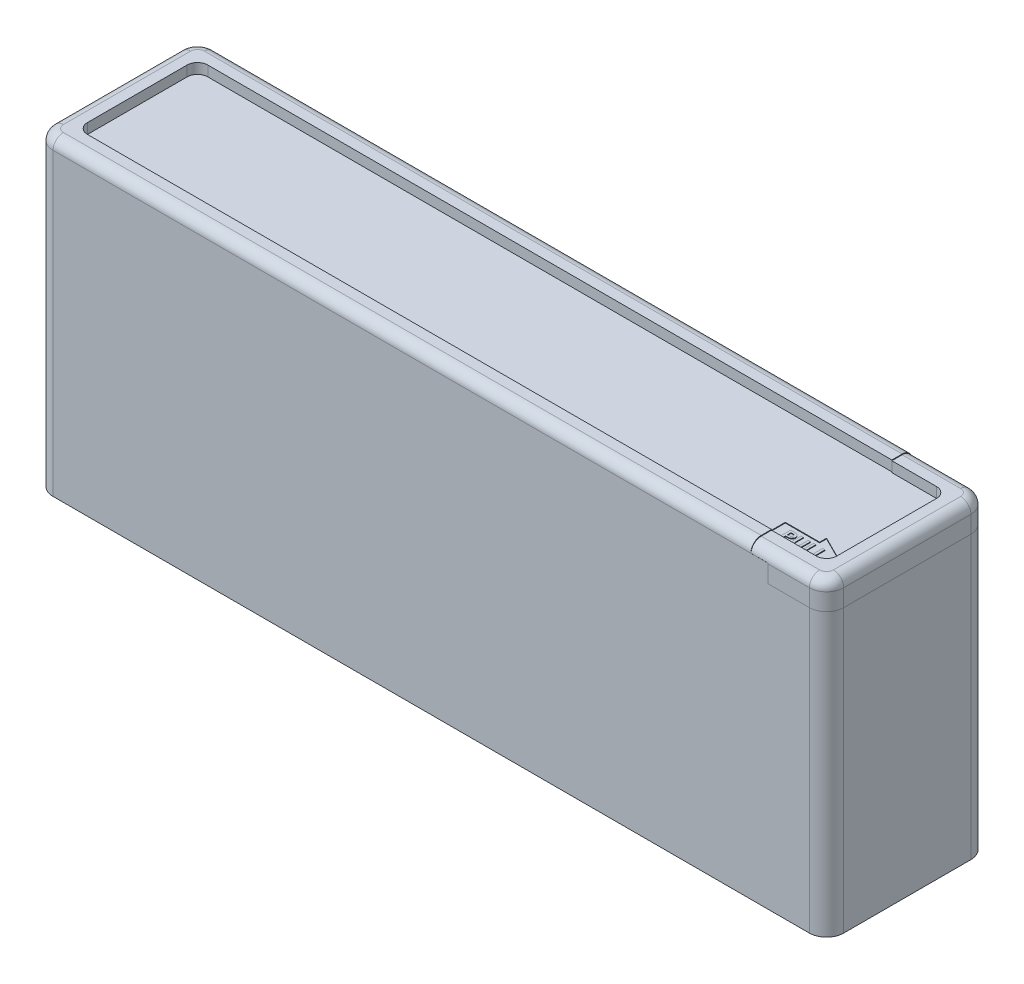
SolidWorks part; units mm, degrees
other "Silica Gel Box"
other "Silica Gel Front"
other "Main Body"
other "Top Slide"
other "Top Trim Add-on"
other "Rectangular Magnet Cover"
other "Circular Magnet Cover 1"
other "Circular Magnet Cover 2"
other "8x1.65 Magnet 2"
other "8x1.65 Magnet 1"
other "20x6x2 Magnet"
other "Drawer"
other "Felt Pad 4"
other "Felt Pad 3"
other "Felt Pad 2"
other "Felt Pad 1"
ref_plane "Front Plane" through (0, 0, 0) normal (0, 0, 1) x (1, 0, 0)
ref_plane "Top Plane" through (0, 0, 0) normal (0, 1, 0) x (1, 0, 0)
ref_plane "Right Plane" through (0, 0, 0) normal (1, 0, 0) x (0, 0, -1)
sketch "Sketch1" plane through (0, 0, 0) normal (0, 1, 0) x (1, 0, 0)
  line L0 (-6, 41) -> (208, 41)
  line L1 (0, 0) -> (202, 0)
  line L2 (0, 0) -> (0, 35)
  line L3 (0, 35) -> (202, 35)
  line L4 (202, 0) -> (202, 35)
  line L5 (0, 0) -> (202, 35) construction
  line L6 (0, 35) -> (202, 0) construction
  line L7 (208, -6) -> (208, 41)
  line L8 (-6, -6) -> (208, -6)
  line L9 (-6, -6) -> (-6, 41)
  point P4 (101, 17.5)
  dimension "D1" = 35
  dimension "D2" = 202
  dimension "D3" = 6
extrude "Boss-Extrude1" add sketch "Sketch1" along normal blind 5
sketch "Sketch2" plane through (0, 0, 0) normal (0, -1, 0) x (1, 0, 0)
  line L4 (-6, 6) -> (-6, -41)
  line L5 (-6, -41) -> (208, -41)
  line L6 (208, -41) -> (208, 6)
  line L7 (208, 6) -> (-6, 6)
  line L8 (-6, 6) -> (-6, -41)
  line L9 (-6, -41) -> (208, -41)
  line L10 (208, -41) -> (208, 6)
  line L11 (208, 6) -> (-6, 6)
  dimension "D1" = 0
extrude "Boss-Extrude2" add sketch "Sketch2" along normal blind 2
sketch "Sketch3" plane through (0, 0, 0) normal (1, 0, 0) x (0, 0, -1)
  line L6 (17.5, 0.5) -> (17.5, 1) construction
  line L8 (0, 0) -> (35, 0) construction
  line L10 (13.5, 0) -> (21.5, 0)
  line L12 (13.5, 1) -> (21.5, 0) construction
  line L13 (13.5, 0) -> (21.5, 1) construction
  arc A1 (21.5, 0) -> (13.5, 0) centre (17.5, -7.5) ccw
  point P4 (17.5, 0.5)
  point P5 (17.5, 0)
  dimension "D1" = 8
  dimension "D2" = 1
extrude "Boss-Extrude3" add sketch "Sketch3" along normal up to surface (202 mm away) up to face at (202, 2.5, -17.5)
sketch "Sketch4" plane through (0, 5, 0) normal (0, 1, 0) x (1, 0, 0)
  line L4 (-6, 41) -> (-6, -6)
  line L5 (-6, -6) -> (208, -6)
  line L6 (208, -6) -> (208, 41)
  line L7 (208, 41) -> (-6, 41)
  line L8 (-6, 41) -> (-6, -6)
  line L9 (-6, -6) -> (208, -6)
  line L10 (208, -6) -> (208, 41)
  line L11 (208, 41) -> (-6, 41)
  line L12 (0, 35) -> (0, 0)
  line L13 (202, 35) -> (0, 35)
  line L14 (202, 0) -> (202, 35)
  line L15 (0, 0) -> (202, 0)
  line L16 (0, 35) -> (0, 0)
  line L17 (202, 35) -> (0, 35)
  line L18 (202, 0) -> (202, 35)
  line L19 (0, 0) -> (202, 0)
  dimension "D1" = 0
  dimension "D2" = 0
extrude "Boss-Extrude4" add sketch "Sketch4" along normal blind 45
sketch "Sketch6" plane through (208, 0, 0) normal (1, 0, 0) x (0, 0, -1)
  line L4 (-6, 50) -> (-6, -2)
  line L5 (-6, -2) -> (41, -2)
  line L6 (41, -2) -> (41, 50)
  line L7 (41, 50) -> (-6, 50)
  line L8 (-6, 50) -> (-6, -2)
  line L9 (-6, -2) -> (41, -2)
  line L10 (41, -2) -> (41, 50)
  line L11 (41, 50) -> (-6, 50)
  dimension "D1" = 0
extrude "Boss-Extrude5" add sketch "Sketch6" along normal blind 16
sketch "Sketch7" plane through (0, 50, 0) normal (0, 1, 0) x (1, 0, 0)
  line L0 (202, 21.5) -> (202, 35) construction
  line L1 (207, 38) -> (202, 38)
  line L2 (207, 38) -> (207, -3)
  line L3 (207, -3) -> (202, -3)
  line L4 (202, 38) -> (202, -3)
  line L5 (207, 38) -> (202, -3) construction
  line L6 (207, -3) -> (202, 38) construction
  line L7 (202, 35) -> (0, 35) construction
  line L8 (0, 0) -> (202, 0) construction
  point P4 (204.5, 17.5)
  dimension "D1" = 3
  dimension "D2" = 3
  dimension "D3" = 5
extrude "Cut-Extrude1" cut sketch "Sketch7" against normal blind 50.1
sketch "Sketch8" plane through (207, 0, 0) normal (-1, 0, 0) x (0, 0, 1)
  line L0 (3, -0.1) -> (3, 50) construction
  line L1 (-38, 50) -> (3, 50)
  line L2 (-38, 50) -> (-38, 0)
  line L3 (-38, 0) -> (3, 0)
  line L4 (3, 50) -> (3, 0)
  line L5 (-38, 50) -> (3, 0) construction
  line L6 (-38, 0) -> (3, 50) construction
  point P4 (-17.5, 25)
  dimension "D1" = 50
extrude "Boss-Extrude6" add sketch "Sketch8" along normal blind 5 separate body
sketch "Sketch9" plane through (207, 0, 0) normal (-1, 0, 0) x (0, 0, 1)
  line L4 (3, 50) -> (-38, 50)
  line L5 (-38, 50) -> (-38, -0.1)
  line L6 (-38, -0.1) -> (3, -0.1)
  line L7 (3, -0.1) -> (3, 50)
  line L8 (3, 50) -> (-38, 50)
  line L9 (-38, 50) -> (-38, -0.1)
  line L10 (-38, -0.1) -> (3, -0.1)
  line L11 (3, -0.1) -> (3, 50)
  dimension "D1" = 0
extrude "Cut-Extrude2" cut sketch "Sketch9" against normal blind 14
sketch "Sketch10" plane through (221, 0, 0) normal (-1, 0, 0) x (0, 0, 1)
  line L0 (3, -0.1) -> (3, 50) construction
  line L1 (-38, 50) -> (3, 50)
  line L2 (-38, 50) -> (-38, 0)
  line L3 (-38, 0) -> (3, 0)
  line L4 (3, 50) -> (3, 0)
  line L5 (-38, 50) -> (3, 0) construction
  line L6 (-38, 0) -> (3, 50) construction
  point P4 (-17.5, 25)
  dimension "D1" = 50
extrude "Boss-Extrude7" add sketch "Sketch10" along normal blind 3 separate body
sketch "Sketch12" plane through (218, 0, 0) normal (-1, 0, 0) x (0, 0, 1)
  line L0 (-35, 47) -> (-35, 3)
  line L1 (-35, 3) -> (0, 3)
  line L2 (0, 3) -> (0, 47)
  line L3 (0, 47) -> (-35, 47)
  line L4 (-38, 50) -> (-38, 0)
  line L5 (-38, 0) -> (3, 0)
  line L6 (3, 0) -> (3, 50)
  line L7 (3, 50) -> (-38, 50)
  line L8 (-38, 50) -> (-38, 0)
  line L9 (-38, 0) -> (3, 0)
  line L10 (3, 0) -> (3, 50)
  line L11 (3, 50) -> (-38, 50)
  dimension "D1" = 0
  dimension "D2" = 3
extrude "Boss-Extrude8" add sketch "Sketch12" along normal blind 11
chamfer "Chamfer1" distance 8 angle 45 4 edges at (212.5, 3, 0) (212.5, 3, -35) (212.5, 47, 0) (212.5, 47, -35)
fillet "Fillet1" radius 3 5 edges at (211.5, -0.1, -38) (221, 24.95, -38) (221, -0.1, -17.5) (221, 24.95, 3) (211.5, -0.1, 3)
fillet "Fillet2" radius 3 5 edges at (221, 25, 3) (214, 0, 3) (221, 0, -17.5) (214, 0, -38) (221, 25, -38)
fillet "Fillet3" radius 3 2 edges at (204.5, 0, -38) (204.5, 0, 3)
sketch "Sketch15" plane through (207, 0, 0) normal (-1, 0, 0) x (0, 0, 1)
  line L0 (-38, 50) -> (-31, 43) construction
  line L1 (-27, 47) -> (-35, 39) construction
  line L2 (-17.5, 50) -> (-17.5, 0) construction
  line L3 (3, 50) -> (-38, 50) construction
  line L4 (-35, 0) -> (0, 0) construction
  line L5 (-17.5, 25) -> (3, 25) construction
  line L8 (3, 3) -> (3, 50) construction
  circle A0 centre (-34.5, 46.5) radius 1.1
  circle A1 centre (-0.5, 46.5) radius 1.1
  circle A4 centre (-0.5, 3.5) radius 1.1
  circle A5 centre (-34.5, 3.5) radius 1.1
  dimension "D1" = 2.2
extrude "Cut-Extrude3" cut sketch "Sketch15" against normal blind 11
sketch "Sketch16" plane through (218, 0, 0) normal (-1, 0, 0) x (0, 0, 1)
  line L0 (-38, 50) -> (-31, 43) construction
  line L1 (-27, 47) -> (-35, 39) construction
  line L2 (-17.5, 25) -> (3, 25) construction
  line L5 (-17.5, 50) -> (-17.5, 0) construction
  line L6 (3, 50) -> (-38, 50) construction
  line L7 (-35, 0) -> (0, 0) construction
  line L8 (-35, 39) -> (-27, 47) construction
  line L9 (-32.8262, 48.1738) -> (-35.1127, 48.7865)
  line L10 (-35.1127, 48.7865) -> (-36.7865, 47.1127)
  line L11 (-36.7865, 47.1127) -> (-36.1738, 44.8262)
  line L12 (-36.1738, 44.8262) -> (-33.8873, 44.2135)
  line L13 (-33.8873, 44.2135) -> (-32.2135, 45.8873)
  line L14 (-32.2135, 45.8873) -> (-32.8262, 48.1738)
  line L15 (-2.1738, 48.1738) -> (0.1127, 48.7865)
  line L16 (-1.1127, 44.2135) -> (-2.7865, 45.8873)
  line L17 (-2.7865, 45.8873) -> (-2.1738, 48.1738)
  line L18 (1.1738, 44.8262) -> (-1.1127, 44.2135)
  line L19 (1.7865, 47.1127) -> (1.1738, 44.8262)
  line L20 (0.1127, 48.7865) -> (1.7865, 47.1127)
  line L33 (3, 3) -> (3, 50) construction
  line L34 (1.7865, 2.8873) -> (1.1738, 5.1738)
  line L35 (1.1738, 5.1738) -> (-1.1127, 5.7865)
  line L36 (-1.1127, 5.7865) -> (-2.7865, 4.1127)
  line L37 (-2.7865, 4.1127) -> (-2.1738, 1.8262)
  line L38 (-2.1738, 1.8262) -> (0.1127, 1.2135)
  line L39 (0.1127, 1.2135) -> (1.7865, 2.8873)
  line L40 (-33.8873, 5.7865) -> (-32.2135, 4.1127)
  line L41 (-32.2135, 4.1127) -> (-32.8262, 1.8262)
  line L42 (-32.8262, 1.8262) -> (-35.1127, 1.2135)
  line L43 (-35.1127, 1.2135) -> (-36.7865, 2.8873)
  line L44 (-36.7865, 2.8873) -> (-36.1738, 5.1738)
  line L45 (-36.1738, 5.1738) -> (-33.8873, 5.7865)
  circle A0 centre (-34.5, 46.5) radius 2.05 construction
  circle A1 centre (-0.5, 46.5) radius 2.05 construction
  circle A4 centre (-0.5, 3.5) radius 2.05 construction
  circle A5 centre (-34.5, 3.5) radius 2.05 construction
  dimension "D1" = 4.1
extrude "Cut-Extrude4" cut sketch "Sketch16" along normal blind 2.2
sketch "Sketch17" plane through (202, 0, 0) normal (-1, 0, 0) x (0, 0, 1)
  line L0 (-8, 47) -> (-27, 47) construction
  circle A0 centre (-25.5, 45) radius 1
  circle A3 centre (-0.5, 3.5) radius 1.1
  circle A5 centre (-0.5, 46.5) radius 1.1
  circle A6 centre (-0.5, 46.5) radius 1.1
  circle A7 centre (-34.5, 46.5) radius 1.1
  circle A8 centre (-34.5, 46.5) radius 1.1
  circle A13 centre (-21.5, 45) radius 1
  circle A14 centre (-17.5, 45) radius 1
  circle A15 centre (-13.5, 45) radius 1
  circle A16 centre (-9.5, 45) radius 1
  circle A17 centre (-25.5, 41) radius 1
  circle A18 centre (-21.5, 41) radius 1
  circle A19 centre (-17.5, 41) radius 1
  circle A20 centre (-13.5, 41) radius 1
  circle A21 centre (-9.5, 41) radius 1
  circle A22 centre (-25.5, 37) radius 1
  circle A23 centre (-21.5, 37) radius 1
  circle A24 centre (-17.5, 37) radius 1
  circle A25 centre (-13.5, 37) radius 1
  circle A26 centre (-9.5, 37) radius 1
  circle A27 centre (-25.5, 33) radius 1
  circle A28 centre (-21.5, 33) radius 1
  circle A29 centre (-17.5, 33) radius 1
  circle A30 centre (-13.5, 33) radius 1
  circle A31 centre (-9.5, 33) radius 1
  circle A32 centre (-25.5, 29) radius 1
  circle A33 centre (-21.5, 29) radius 1
  circle A34 centre (-17.5, 29) radius 1
  circle A35 centre (-13.5, 29) radius 1
  circle A36 centre (-9.5, 29) radius 1
  circle A37 centre (-25.5, 25) radius 1
  circle A38 centre (-21.5, 25) radius 1
  circle A39 centre (-17.5, 25) radius 1
  circle A40 centre (-13.5, 25) radius 1
  circle A41 centre (-9.5, 25) radius 1
  circle A42 centre (-25.5, 21) radius 1
  circle A43 centre (-21.5, 21) radius 1
  circle A44 centre (-17.5, 21) radius 1
  circle A45 centre (-13.5, 21) radius 1
  circle A46 centre (-9.5, 21) radius 1
  circle A47 centre (-25.5, 17) radius 1
  circle A48 centre (-21.5, 17) radius 1
  circle A49 centre (-17.5, 17) radius 1
  circle A50 centre (-13.5, 17) radius 1
  circle A51 centre (-9.5, 17) radius 1
  circle A52 centre (-25.5, 13) radius 1
  circle A53 centre (-21.5, 13) radius 1
  circle A54 centre (-17.5, 13) radius 1
  circle A55 centre (-13.5, 13) radius 1
  circle A56 centre (-9.5, 13) radius 1
  circle A57 centre (-25.5, 9) radius 1
  circle A58 centre (-21.5, 9) radius 1
  circle A59 centre (-17.5, 9) radius 1
  circle A60 centre (-13.5, 9) radius 1
  circle A61 centre (-9.5, 9) radius 1
  circle A62 centre (-25.5, 5) radius 1
  circle A63 centre (-21.5, 5) radius 1
  circle A64 centre (-17.5, 5) radius 1
  circle A65 centre (-13.5, 5) radius 1
  circle A66 centre (-9.5, 5) radius 1
  circle A67 centre (-29.5, 41) radius 1
  circle A68 centre (-29.5, 37) radius 1
  circle A69 centre (-29.5, 33) radius 1
  circle A70 centre (-29.5, 29) radius 1
  circle A71 centre (-29.5, 25) radius 1
  circle A72 centre (-29.5, 21) radius 1
  circle A73 centre (-29.5, 17) radius 1
  circle A74 centre (-29.5, 13) radius 1
  circle A75 centre (-29.5, 9) radius 1
  circle A77 centre (-33.5, 37) radius 1
  circle A78 centre (-33.5, 33) radius 1
  circle A79 centre (-33.5, 29) radius 1
  circle A80 centre (-33.5, 25) radius 1
  circle A81 centre (-33.5, 21) radius 1
  circle A82 centre (-33.5, 17) radius 1
  circle A83 centre (-33.5, 13) radius 1
  circle A85 centre (-5.5, 41) radius 1
  circle A86 centre (-5.5, 37) radius 1
  circle A87 centre (-5.5, 33) radius 1
  circle A88 centre (-5.5, 29) radius 1
  circle A89 centre (-5.5, 25) radius 1
  circle A90 centre (-5.5, 21) radius 1
  circle A91 centre (-5.5, 17) radius 1
  circle A92 centre (-5.5, 13) radius 1
  circle A93 centre (-5.5, 9) radius 1
  circle A95 centre (-1.5, 37) radius 1
  circle A96 centre (-1.5, 33) radius 1
  circle A97 centre (-1.5, 29) radius 1
  circle A98 centre (-1.5, 25) radius 1
  circle A99 centre (-1.5, 21) radius 1
  circle A100 centre (-1.5, 17) radius 1
  circle A101 centre (-1.5, 13) radius 1
  circle A103 centre (-1.5, 41) radius 1 [skipped]
  circle A104 centre (-33.5, 41) radius 1 [skipped]
  circle A105 centre (-33.5, 9) radius 1 [skipped]
  circle A106 centre (-1.5, 9) radius 1 [skipped]
  circle A107 centre (-0.5, 3.5) radius 1.1
  circle A108 centre (-34.5, 3.5) radius 1.1
  circle A109 centre (-34.5, 3.5) radius 1.1
  dimension "D5" = 2
  dimension "D6" = 2
  dimension "D7" = 1.5
  dimension "D9" = 4
  dimension "D11" = 4
  dimension "D13" = 4
  dimension "D15" = 4
  dimension "D2" = 0
  dimension "D3" = 0
  dimension "D4" = 0
  dimension "D16" = 0
  dimension "D8" = 5
  dimension "D10" = 11
  dimension "D12" = 3
  dimension "D14" = 3
extrude "Cut-Extrude5" cut sketch "Sketch17" against normal up to surface (5 mm away) up to face at (207, 17.4596, -17.5)
sketch "Sketch18" plane through (0, 50, 0) normal (0, 1, 0) x (1, 0, 0)
  line L0 (-6, -6) -> (224, -6) construction
  line L1 (-6, 41) -> (-6, -6) construction
  line L2 (224, 41) -> (-6, 41) construction
  line L3 (-6, -6) -> (207, -6)
  line L4 (-6, 41) -> (-6, -6)
  line L5 (207, 41) -> (-6, 41)
  line L6 (207, 38.2) -> (-3.2, 38.2)
  line L7 (-3.2, 38.2) -> (-3.2, -3.2)
  line L8 (-3.2, -3.2) -> (207, -3.2)
  line L9 (207, 41) -> (207, 38.2)
  line L10 (207, -3) -> (207, 38) construction
  line L11 (207, -3.2) -> (207, -6)
  line L12 (224, 41) -> (-6, 41) construction
  line L13 (224, 38.2) -> (-3.2, 38.2) construction
  line L15 (-3.2, -3.2) -> (224, -3.2) construction
  line L16 (-6, -6) -> (224, -6) construction
  dimension "D1" = 2.8
extrude "Boss-Extrude9" add sketch "Sketch18" along normal blind 5.2
fillet "Fillet4" radius 3 2 edges at (207, 52.6, 3.2) (207, 52.6, -38.2)
sketch "Sketch19" plane through (0, 55.2, 0) normal (0, 1, 0) x (1, 0, 0)
  line L0 (0, 0) -> (202, 0) construction
  line L1 (0, 35) -> (0, 0) construction
  line L2 (202, 35) -> (0, 35) construction
  line L3 (-6, -6) -> (207, -6) construction
  line L4 (-6, 41) -> (-6, -6) construction
  line L5 (207, 41) -> (-6, 41) construction
  line L6 (0, 0) -> (202, 0)
  line L7 (0, 35) -> (0, 0)
  line L8 (202, 35) -> (0, 35)
  line L9 (-6, -6) -> (202, -6)
  line L10 (-6, 41) -> (-6, -6)
  line L11 (202, 41) -> (-6, 41)
  line L16 (202, 0) -> (202, -6)
  line L17 (202, 35) -> (202, 41)
extrude "Boss-Extrude10" add sketch "Sketch19" along normal blind 3
fillet "Fillet5" radius 3 4 edges at (0, 56.7, 0) (-3.2, 52.6, 3.2) (0, 56.7, -35) (-3.2, 52.6, -38.2)
fillet "Fillet6" radius 5 4 edges at (224, 24, 6) (224, 24, -41) (-6, 28.1, -41) (-6, 28.1, 6)
fillet "Fillet7" radius 3 5 edges at (100.5, 58.2, -41) (-4.5355, 58.2, -39.5355) (-6, 58.2, -17.5) (-4.5355, 58.2, 4.5355) (100.5, 58.2, 6)
sketch "Sketch21" plane through (0, 50, 0) normal (0, 1, 0) x (1, 0, 0)
  line L1 (207, -6) -> (219, -6) construction
  line L2 (224, 36) -> (224, -1) construction
  line L3 (219, 41) -> (207, 41) construction
  line L6 (-3.2, -0.2) -> (-3.2, 35.2) construction
  line L8 (202, -3) -> (204.0067, -3.2)
  line L9 (207, -6) -> (219, -6)
  line L10 (224, 36) -> (224, -1)
  line L11 (219, 41) -> (207, 41)
  line L12 (202, 38) -> (204.0067, 38.2)
  line L13 (202, -3) -> (-0.2, -3.2)
  line L14 (-3.2, -0.2) -> (-3.2, 35.2)
  line L15 (-0.2, 38.2) -> (202, 38)
  arc A0 (207, -6) -> (204.0067, -3.2) centre (204.0067, -6.2) ccw construction
  arc A1 (219, -6) -> (224, -1) centre (219, -1) ccw construction
  arc A2 (224, 36) -> (219, 41) centre (219, 36) ccw construction
  arc A3 (204.0067, 38.2) -> (207, 41) centre (204.0067, 41.2) ccw construction
  arc A4 (-3.2, -0.2) -> (-0.2, -3.2) centre (-0.2, -0.2) ccw construction
  arc A5 (-0.2, 38.2) -> (-3.2, 35.2) centre (-0.2, 35.2) ccw construction
  arc A6 (207, -6) -> (204.0067, -3.2) centre (204.0067, -6.2) ccw
  arc A7 (219, -6) -> (224, -1) centre (219, -1) ccw
  arc A8 (224, 36) -> (219, 41) centre (219, 36) ccw
  arc A9 (204.0067, 38.2) -> (207, 41) centre (204.0067, 41.2) ccw
  arc A10 (-3.2, -0.2) -> (-0.2, -3.2) centre (-0.2, -0.2) ccw
  arc A11 (-0.2, 38.2) -> (-3.2, 35.2) centre (-0.2, 35.2) ccw
extrude "Boss-Extrude11" add sketch "Sketch21" along normal blind 5 separate body
sketch "Sketch22" plane through (0, 55, 0) normal (0, 1, 0) x (1, 0, 0)
  line L3 (202, -6) -> (219, -6)
  line L4 (224, -1) -> (224, 36)
  line L5 (219, 41) -> (202, 41)
  line L6 (215, 35) -> (202, 35)
  line L7 (218, 3) -> (218, 32)
  line L8 (202, 0) -> (215, 0)
  line L10 (219, 35) -> (207, 35) construction
  line L11 (218, -1) -> (218, 36) construction
  line L12 (207, 0) -> (219, 0) construction
  line L14 (202, 35) -> (202, 41)
  line L15 (202, 0) -> (202, -6)
  line L16 (207, -6) -> (219, -6) construction
  line L17 (219, 41) -> (207, 41) construction
  arc A0 (219, -6) -> (224, -1) centre (219, -1) ccw construction
  arc A1 (224, 36) -> (219, 41) centre (219, 36) ccw construction
  arc A2 (219, -6) -> (224, -1) centre (219, -1) ccw
  arc A3 (224, 36) -> (219, 41) centre (219, 36) ccw
  arc A4 (215, 35) -> (218, 32) centre (215, 32) cw
  arc A5 (215, 0) -> (218, 3) centre (215, 3) ccw
  dimension "D2" = 3
extrude "Boss-Extrude12" add sketch "Sketch22" along normal blind 3 separate body
fillet "Fillet8" radius 3 5 edges at (210.5, 58, -41) (222.5355, 58, -39.5355) (224, 58, -17.5) (222.5355, 58, 4.5355) (210.5, 58, 6)
sketch "Sketch23" plane through (0, -2, 0) normal (0, -1, 0) x (1, 0, 0)
  line L4 (224, -36) -> (224, 1)
  line L5 (219, 6) -> (-1, 6)
  line L6 (-6, 1) -> (-6, -36)
  line L7 (-1, -41) -> (219, -41)
  line L8 (224, -36) -> (224, 1)
  line L9 (219, 6) -> (-1, 6)
  line L10 (-6, 1) -> (-6, -36)
  line L11 (-1, -41) -> (219, -41)
  arc A4 (224, 1) -> (219, 6) centre (219, 1) ccw
  arc A5 (-1, 6) -> (-6, 1) centre (-1, 1) ccw
  arc A6 (-6, -36) -> (-1, -41) centre (-1, -36) ccw
  arc A7 (219, -41) -> (224, -36) centre (219, -36) ccw
  arc A8 (224, 1) -> (219, 6) centre (219, 1) ccw
  arc A9 (-1, 6) -> (-6, 1) centre (-1, 1) ccw
  arc A10 (-6, -36) -> (-1, -41) centre (-1, -36) ccw
  arc A11 (219, -41) -> (224, -36) centre (219, -36) ccw
  dimension "D1" = 0
extrude "Boss-Extrude13" add sketch "Sketch23" along normal blind 30
sketch "Sketch24" plane through (0, -32, 0) normal (0, -1, 0) x (1, 0, 0)
  line L0 (219, 6) -> (-1, 6) construction
  line L1 (-1, -41) -> (219, -41) construction
  line L2 (-6, 1) -> (-6, -36) construction
  line L3 (224, -36) -> (224, 1) construction
  circle A0 centre (4, -4) radius 6.05
  circle A1 centre (4, -31) radius 6.05
  circle A2 centre (214, -31) radius 6.05
  circle A3 centre (214, -4) radius 6.05
  dimension "D1" = 12.1
  dimension "D2" = 10
  dimension "D3" = 10
  dimension "D4" = 10
  dimension "D5" = 10
extrude "Cut-Extrude6" cut sketch "Sketch24" against normal blind 1.5
sketch "Sketch25" plane through (0, -32, 0) normal (0, -1, 0) x (1, 0, 0)
  line L0 (-6, 1) -> (-6, -36) construction
  line L1 (34, -2.35) -> (114.4, -2.35)
  line L2 (34, -2.35) -> (34, -32.65)
  line L3 (34, -32.65) -> (114.4, -32.65)
  line L4 (114.4, -2.35) -> (114.4, -32.65)
  line L5 (34, -2.35) -> (114.4, -32.65) construction
  line L6 (34, -32.65) -> (114.4, -2.35) construction
  point P4 (74.2, -17.5)
  point P7 (-6, -17.5)
  dimension "D1" = 80.4
  dimension "D2" = 30.3
  dimension "D3" = 40
extrude "Cut-Extrude7" cut sketch "Sketch25" against normal blind 25.1
sketch "Sketch26" plane through (0, -6.9, 0) normal (0, -1, 0) x (1, 0, 0)
  line L0 (74.2, -2.35) -> (74.2, -32.65) construction
  line L1 (114.4, -2.35) -> (34, -2.35) construction
  line L2 (34, -32.65) -> (114.4, -32.65) construction
  line L4 (76.75, -7.4) -> (71.65, -7.4)
  line L5 (77.25, -7.9) -> (77.25, -27.1)
  line L6 (76.75, -27.6) -> (71.65, -27.6)
  line L7 (71.15, -7.9) -> (71.15, -27.1)
  line L8 (74.2, -27.6) -> (74.2, -7.4) construction
  line L9 (77.25, -17.5) -> (71.15, -17.5) construction
  arc A0 (77.25, -27.1) -> (76.75, -27.6) centre (76.75, -27.1) cw
  arc A1 (71.65, -27.6) -> (71.15, -27.1) centre (71.65, -27.1) cw
  arc A2 (71.65, -7.4) -> (71.15, -7.9) centre (71.65, -7.9) ccw
  arc A3 (76.75, -7.4) -> (77.25, -7.9) centre (76.75, -7.9) cw
  point P6 (74.2, -17.5)
  point P12 (77.25, -27.6)
  point P15 (71.15, -27.6)
  point P21 (77.25, -7.4)
  dimension "D3" = 0.5
  dimension "D1" = 20.2
  dimension "D2" = 6.1
extrude "Cut-Extrude8" cut sketch "Sketch26" against normal blind 3
sketch "Sketch27" plane through (0, -6.9, 0) normal (0, -1, 0) x (1, 0, 0)
  line L4 (77.25, -27.1) -> (77.25, -7.9)
  line L5 (76.75, -7.4) -> (71.65, -7.4)
  line L6 (71.15, -7.9) -> (71.15, -27.1)
  line L7 (71.65, -27.6) -> (76.75, -27.6)
  line L8 (77.25, -27.1) -> (77.25, -7.9)
  line L9 (76.75, -7.4) -> (71.65, -7.4)
  line L10 (71.15, -7.9) -> (71.15, -27.1)
  line L11 (71.65, -27.6) -> (76.75, -27.6)
  arc A4 (76.75, -27.6) -> (77.25, -27.1) centre (76.75, -27.1) ccw
  arc A5 (77.25, -7.9) -> (76.75, -7.4) centre (76.75, -7.9) ccw
  arc A6 (71.65, -7.4) -> (71.15, -7.9) centre (71.65, -7.9) ccw
  arc A7 (71.15, -27.1) -> (71.65, -27.6) centre (71.65, -27.1) ccw
  arc A8 (76.75, -27.6) -> (77.25, -27.1) centre (76.75, -27.1) ccw
  arc A9 (77.25, -7.9) -> (76.75, -7.4) centre (76.75, -7.9) ccw
  arc A10 (71.65, -7.4) -> (71.15, -7.9) centre (71.65, -7.9) ccw
  arc A11 (71.15, -27.1) -> (71.65, -27.6) centre (71.65, -27.1) ccw
  dimension "D1" = 0
extrude "Boss-Extrude14" add sketch "Sketch27" against normal blind 1 separate body
sketch "Sketch28" plane through (0, -32, 0) normal (0, -1, 0) x (1, 0, 0)
  line L9 (114.4, -32.65) -> (114.4, -2.35) construction
  line L10 (34, -2.35) -> (34, -32.65) construction
  line L11 (114.4, -32.65) -> (114.4, -2.35) construction
  circle A4 centre (36, -17.5) radius 7.5
  circle A5 centre (112.4, -17.5) radius 7.5
  point P10 (114.4, -17.5)
  dimension "D1" = 15
  dimension "D2" = 2
  dimension "D3" = 2
extrude "Cut-Extrude9" cut sketch "Sketch28" against normal blind 2
fillet "Fillet10" radius 5 2 edges at (119.9, -30, -17.5) (28.5, -30, -17.5)
sketch "Sketch29" plane through (0, -32, 0) normal (0, -1, 0) x (1, 0, 0)
  line L0 (114.4, -2.35) -> (34, -2.35) construction
  line L1 (134.7, -2.35) -> (200, -2.35)
  line L2 (134.7, -2.35) -> (134.7, -32.65)
  line L3 (134.7, -32.65) -> (200, -32.65)
  line L4 (200, -2.35) -> (200, -32.65)
  line L5 (134.7, -2.35) -> (200, -32.65) construction
  line L6 (134.7, -32.65) -> (200, -2.35) construction
  line L7 (34, -32.65) -> (114.4, -32.65) construction
  line L8 (224, -36) -> (224, 1) construction
  point P4 (167.35, -17.5)
  dimension "D1" = 65.3
  dimension "D2" = 24
extrude "Cut-Extrude10" cut sketch "Sketch29" against normal blind 15
sketch "Sketch30" plane through (0, -17, 0) normal (0, -1, 0) x (1, 0, 0)
  line L0 (134.7, -2.35) -> (134.7, -32.65) construction
  line L1 (134.7, -2.35) -> (134.7, -32.65) construction
  line L2 (200, -32.65) -> (200, -2.35) construction
  circle A0 centre (140.7, -17.5) radius 4.05
  circle A1 centre (194, -17.5) radius 4.05
  point P6 (134.7, -17.5)
  dimension "D1" = 8.1
  dimension "D2" = 6
  dimension "D3" = 6
extrude "Cut-Extrude11" cut sketch "Sketch30" against normal blind 2.8
sketch "Sketch31" plane through (0, -17, 0) normal (0, -1, 0) x (1, 0, 0)
  circle A0 centre (194, -17.5) radius 4.05 construction
  circle A1 centre (140.7, -17.5) radius 4.05 construction
  circle A2 centre (194, -17.5) radius 4.05
  circle A3 centre (140.7, -17.5) radius 4.05
extrude "Boss-Extrude15" add sketch "Sketch31" against normal blind 1 separate body
sketch "Sketch32" plane through (0, -17, 0) normal (0, -1, 0) x (1, 0, 0)
  line L14 (199.9, -32.55) -> (199.9, -2.45)
  line L15 (134.8, -32.55) -> (199.9, -32.55)
  line L16 (134.8, -2.45) -> (134.8, -32.55)
  line L17 (199.9, -2.45) -> (134.8, -2.45)
  line L18 (199.9, -32.55) -> (199.9, -2.45)
  line L19 (134.8, -32.55) -> (199.9, -32.55)
  line L20 (134.8, -2.45) -> (134.8, -32.55)
  line L21 (199.9, -2.45) -> (134.8, -2.45)
  dimension "D1" = 0.1
extrude "Boss-Extrude16" add sketch "Sketch32" along normal up to surface (15 mm away) separate body up to face at (167.35, -32, -17.5)
shell "Shell1" thickness 3 removed face at (134.8, -24.5, -17.5)
sketch "Sketch34" plane through (0, -20, 0) normal (0, -1, 0) x (1, 0, 0)
  circle A0 centre (140.7, -17.5) radius 4.05 construction
  circle A1 centre (194, -17.5) radius 4.05 construction
  circle A2 centre (140.7, -17.5) radius 4.05
  circle A3 centre (194, -17.5) radius 4.05
extrude "Cut-Extrude12" cut sketch "Sketch34" against normal blind 2
sketch "Sketch35" plane through (0, -32, 0) normal (0, -1, 0) x (1, 0, 0)
  line L0 (200, -32.65) -> (200, -2.35) construction
  line L1 (134.7, -2.35) -> (134.7, -32.65) construction
  line L2 (200, -32.65) -> (200, -2.35) construction
  line L3 (134.7, -2.35) -> (134.7, -32.65) construction
  line L4 (200, -24.7284) -> (200, -10.2716)
  line L5 (134.7, -10.2716) -> (134.7, -24.7284)
  arc A0 (134.7, -10.2716) -> (134.7, -24.7284) centre (136.7, -17.5) ccw
  arc A1 (200, -24.7284) -> (200, -10.2716) centre (198, -17.5) ccw
  point P6 (200, -17.5)
  dimension "D1" = 15
  dimension "D2" = 2
  dimension "D3" = 2
extrude "Cut-Extrude13" cut sketch "Sketch35" against normal blind 2
fillet "Fillet11" radius 5 2 edges at (205.5, -30, -17.5) (129.2, -30, -17.5)
sketch "Sketch36" plane through (0, 55, 0) normal (0, 1, 0) x (1, 0, 0)
  line L0 (199, 1) -> (219, 1) construction
  line L1 (224, -1) -> (224, 36) construction
  line L2 (207, -6) -> (219, -6) construction
  line L3 (199, 4) -> (219, 4) construction
  line L4 (199, 4) -> (199, 7)
  line L5 (199, 7) -> (209, 7)
  line L6 (209, 7) -> (209, 9)
  line L7 (209, 9) -> (219, 4)
  line L11 (199, 1) -> (199, 4)
  line L12 (199, 1) -> (209, 1)
  line L13 (209, 1) -> (209, -1)
  line L14 (209, -1) -> (219, 4)
  dimension "D1" = 5
  dimension "D2" = 7
  dimension "D3" = 20
  dimension "D5" = 3
  dimension "D6" = 10
  dimension "D7" = 2
  dimension "D8" = 2
  dimension "D4" = 3
extrude "Cut-Extrude14" cut sketch "Sketch36" against normal blind 0.2 contours L13 L14 L7 L6 L5 L4 L11 L12 region at (207.7879, 55, -4)
sketch "Sketch37" plane through (0, 54.8, 0) normal (0, 1, 0) x (1, 0, 0)
  line L0 (219, 4) -> (199, 4) construction
  line L1 (199, 1) -> (199, 7) construction
  line L2 (199, 2.3049) -> (215.6099, 2.3049) construction
  line L3 (209, -1) -> (219, 4) construction
  text T0 "<b>PULL</b>" font "Touche Semibold" height 3.5
extrude "Boss-Extrude17" add sketch "Sketch37" along normal blind 0.2
sketch "Sketch38" plane through (0, -3.9, 0) normal (0, -1, 0) x (1, 0, 0)
  line L0 (71.2964, -7.5464) -> (77.1036, -27.4536) construction
  line L1 (77.1036, -7.5464) -> (71.2964, -27.4536) construction
  line L3 (72.2, -27.5) -> (76.2, -27.5)
  line L4 (71.2, -26.5) -> (71.2, -8.5)
  line L5 (72.2, -7.5) -> (76.2, -7.5)
  line L6 (77.2, -26.5) -> (77.2, -8.5)
  line L7 (74.2, -7.5) -> (74.2, -27.5) construction
  line L8 (71.2, -17.5) -> (77.2, -17.5) construction
  arc A0 (71.65, -7.4) -> (71.15, -7.9) centre (71.65, -7.9) ccw construction
  arc A1 (76.75, -27.6) -> (77.25, -27.1) centre (76.75, -27.1) ccw construction
  arc A2 (77.25, -7.9) -> (76.75, -7.4) centre (76.75, -7.9) ccw construction
  arc A3 (71.15, -27.1) -> (71.65, -27.6) centre (71.65, -27.1) ccw construction
  arc A4 (76.2, -7.5) -> (77.2, -8.5) centre (76.2, -8.5) cw
  arc A5 (71.2, -8.5) -> (72.2, -7.5) centre (72.2, -8.5) cw
  arc A6 (76.2, -27.5) -> (77.2, -26.5) centre (76.2, -26.5) ccw
  arc A7 (72.2, -27.5) -> (71.2, -26.5) centre (72.2, -26.5) cw
  point P16 (74.2, -17.5)
  point P22 (77.2, -7.5)
  point P27 (77.2, -27.5)
  point P31 (71.2, -27.5)
  dimension "D3" = 1
  dimension "D1" = 20
  dimension "D2" = 6
extrude "Boss-Extrude18" add sketch "Sketch38" along normal blind 2 separate body
sketch "Sketch39" plane through (0, -14.2, 0) normal (0, -1, 0) x (1, 0, 0)
  circle A0 centre (140.7, -17.5) radius 4
  circle A1 centre (194, -17.5) radius 4
  dimension "D1" = 8
extrude "Boss-Extrude19" add sketch "Sketch39" along normal blind 1.65 separate body
sketch "Sketch40" plane through (0, -30.5, 0) normal (0, -1, 0) x (1, 0, 0)
  circle A0 centre (4, -4) radius 6
  circle A1 centre (4, -31) radius 6
  circle A2 centre (214, -31) radius 6
  circle A3 centre (214, -4) radius 6
  dimension "D1" = 12
extrude "Boss-Extrude20" add sketch "Sketch40" along normal blind 2.5 separate body
